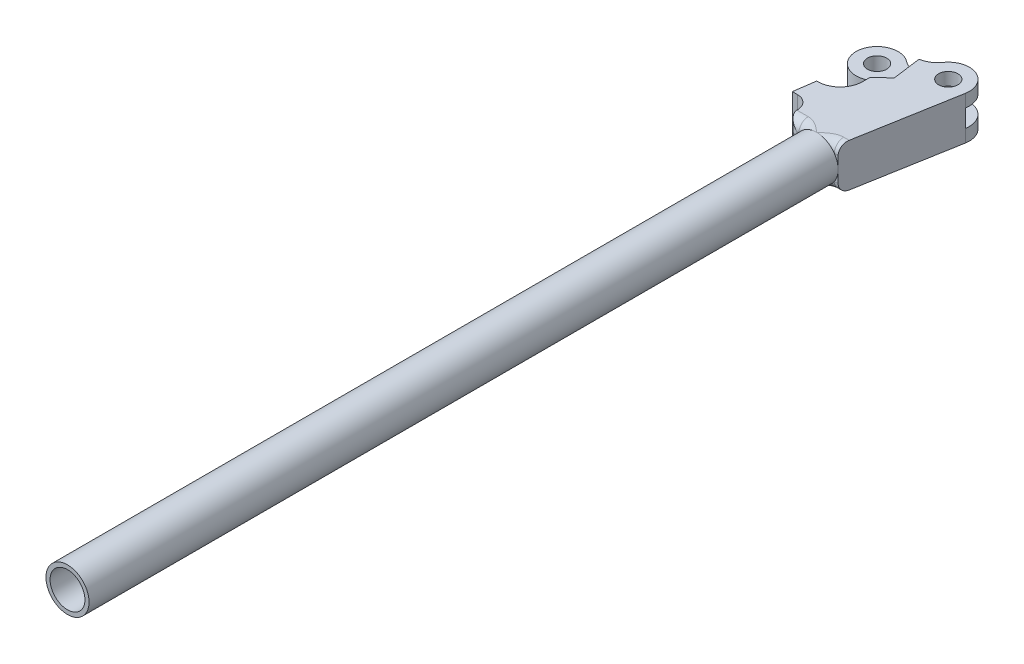
SolidWorks part; units mm, degrees
material "1.7243 (18CrMo4)"
ref_plane "Alzado" through (0, 0, 0) normal (0, 0, 1) x (1, 0, 0)
ref_plane "Planta" through (0, 0, 0) normal (0, 1, 0) x (1, 0, 0)
ref_plane "Vista lateral" through (0, 0, 0) normal (1, 0, 0) x (0, 0, -1)
sketch "Croquis1" plane through (0, 0, 0) normal (0, 0, 1) x (1, 0, 0)
  circle A0 centre (0, 0) radius 9.3
  circle A1 centre (0, 0) radius 11.5
  dimension "D1" = 18.6
  dimension "D2" = 23
extrude "Saliente-Extruir1" add sketch "Croquis1" along normal blind 400
sketch "Croquis2" plane through (0, 0, 0) normal (0, 0, -1) x (-1, 0, 0)
  line L1 (-27, -11.5) -> (27, -11.5)
  line L2 (-27, -11.5) -> (-27, 11.5)
  line L3 (-27, 11.5) -> (27, 11.5)
  line L4 (27, -11.5) -> (27, 11.5)
  line L5 (-27, -11.5) -> (27, 11.5) construction
  line L6 (-27, 11.5) -> (27, -11.5) construction
  point P0 (0, 0)
  dimension "D1" = 23
  dimension "D2" = 54
extrude "Saliente-Extruir2" add sketch "Croquis2" along normal blind 78.8
sketch "Croquis3" plane through (0, 11.5, 0) normal (0, 1, 0) x (1, 0, 0)
  line L0 (0, 0) -> (11.5, 0) construction
  line L1 (0, 0) -> (27, 0) construction
  line L5 (11.5, 0) -> (25.3946, 78.8)
  line L6 (-27, 78.8) -> (27, 78.8) construction
  line L7 (11.5, 0) -> (27, 0)
  line L8 (27, 0) -> (27, 78.8)
  line L9 (27, 78.8) -> (25.3946, 78.8)
  dimension "D1" = 11.5
  dimension "D2" = 80
extrude "Cortar-Extruir1" cut sketch "Croquis3" against normal blind 23
sketch "Croquis4" plane through (0, 11.5, 0) normal (0, 1, 0) x (1, 0, 0)
  line L0 (0.0968, 0) -> (10.6198, 59.6793)
  line L1 (10.6198, 59.6793) -> (-22.3802, 59.6793) construction
  line L2 (-22.3802, 59.6793) -> (-22.3802, 54.6793) construction
  line L3 (-25.3191, 18.04) -> (14.6809, 18.04) construction
  line L4 (-5.3191, 18.04) -> (-5.3191, 0) construction
  line L5 (-11.1502, 54.6793) -> (-11.1502, 35.74)
  line L6 (-23.1502, 23.74) -> (-25.3191, 23.74)
  line L7 (-15.5376, 0) -> (-5.3191, 0)
  line L8 (0, 0) -> (11.5, 0) construction
  line L9 (25.3946, 78.8) -> (11.5, 0) construction
  line L10 (-25.3191, 23.74) -> (-25.3191, 12.34)
  line L11 (-25.3191, 12.34) -> (-22.5376, 12.34)
  line L12 (-15.5376, 5.34) -> (-15.5376, 0)
  line L13 (-27, 0) -> (0, 0) construction
  circle A1 centre (10.6198, 59.6793) radius 5.15
  circle A2 centre (10.6198, 59.6793) radius 11.23
  circle A3 centre (-22.3802, 54.6793) radius 5.15
  circle A4 centre (-22.3802, 54.6793) radius 11.23
  arc A5 (-15.5376, 5.34) -> (-22.5376, 12.34) centre (-22.5376, 5.34) ccw
  arc A6 (-11.1502, 35.74) -> (-23.1502, 23.74) centre (-23.1502, 35.74) cw
  dimension "D2" = 11.23
  dimension "D3" = 10.3
  dimension "D4" = 22.46
  dimension "D7" = 22.46
  dimension "D8" = 10.3
  dimension "D11" = 7
  dimension "D13" = 12
  dimension "D1" = 60.6
  dimension "D5" = 33
  dimension "D6" = 5
  dimension "D9" = 40
  dimension "D10" = 18.04
  dimension "D12" = 11.4
extrude "Cortar-Extruir2" cut sketch "Croquis4" against normal blind 23 contours A1
sketch "Croquis5" plane through (0, 11.5, 0) normal (0, 1, 0) x (1, 0, 0)
  circle A0 centre (-22.3802, 54.6793) radius 11.23
extrude "Saliente-Extruir4" add sketch "Croquis5" against normal blind 23
extrude "Cortar-Extruir4" cut sketch "Croquis4<6>" against normal blind 23 contours A3
sketch "Croquis4<6>" plane through (0, 11.5, 0) normal (0, 1, 0) x (1, 0, 0) same geometry as "Croquis4"
sketch "Croquis6" plane through (0, 11.5, 0) normal (0, 1, 0) x (1, 0, 0)
  line L0 (-27, 78.8) -> (-27, 64.9151)
  line L1 (-27, 78.8) -> (25.3946, 78.8)
  line L3 (21.6792, 57.7293) -> (25.3946, 78.8)
  arc A0 (-15.4635, 63.5265) -> (1.3928, 66.0805) centre (-8.2415, 72.7643) ccw
  arc A2 (-15.4635, 63.5265) -> (-27, 64.9151) centre (-22.3802, 54.6793) ccw
  arc A4 (21.6792, 57.7293) -> (1.3928, 66.0805) centre (10.6198, 59.6793) ccw
extrude "Cortar-Extruir6" cut sketch "Croquis6" against normal blind 23
sketch "Croquis7" plane through (0, 11.5, 0) normal (0, 1, 0) x (1, 0, 0)
  line L0 (-11.1502, 54.6793) -> (-11.1502, 35.74)
  line L1 (-27, 44.4436) -> (-27, 0)
  line L2 (-27, 0) -> (-15.5376, 0)
  line L3 (-15.5376, 0) -> (-15.5376, 5.34)
  line L4 (-22.5376, 12.34) -> (-25.3191, 12.34)
  line L5 (-25.3191, 12.34) -> (-25.3191, 23.74)
  line L6 (-25.3191, 23.74) -> (-23.1502, 23.74)
  arc A0 (-27, 44.4436) -> (-11.1502, 54.6793) centre (-22.3802, 54.6793) ccw
  arc A1 (-23.1502, 23.74) -> (-11.1502, 35.74) centre (-23.1502, 35.74) ccw
  arc A2 (-15.5376, 5.34) -> (-22.5376, 12.34) centre (-22.5376, 5.34) ccw
extrude "Cortar-Extruir7" cut sketch "Croquis7" against normal blind 23
fillet "Redondeo2" radius 5 5 edges at (5.75, -11.5, 0) (-7.7688, -11.5, 0) (5.75, 11.5, 0) (-7.7688, 11.5, 0) (-15.5376, 0, 0)
fillet "Redondeo3" radius 5 1 edges at (-11.1502, 0, -54.6793) type face fillet first side face at (-11.1502, 0, -45.2097) second side face at (-22.8906, 0, -54.4305)
sketch "Croquis11" plane through (0, 11.5, 0) normal (0, 1, 0) x (1, 0, 0)
  circle A0 centre (10.6198, 59.6793) radius 11.23
extrude "Cortar-Extruir9" cut sketch "Croquis11" against normal blind 4.72 and the other way blind 4.72 from offset 11.5 contours A0 offset against normal yes
sketch "Croquis13" plane through (0, 11.5, 0) normal (0, 1, 0) x (1, 0, 0)
  circle A0 centre (-22.3802, 54.6793) radius 11.23
extrude "Cortar-Extruir11" cut sketch "Croquis13" against normal blind 6.78
sketch "Croquis14" plane through (0, -11.5, 0) normal (0, -1, 0) x (1, 0, 0)
  circle A0 centre (-22.3802, -54.6793) radius 11.23
extrude "Cortar-Extruir12" cut sketch "Croquis14" against normal blind 6.78
sketch "Croquis15" plane through (0, 11.5, 0) normal (0, 1, 0) x (1, 0, 0)
  line L0 (-11.1502, 39.6927) -> (-4.4014, 45.8886)
  line L1 (-4.4014, 45.8886) -> (-6.4849, 61.1709)
  arc A1 (-18.0694, 44.3097) -> (-15.4635, 63.5265) centre (-22.3802, 54.6793) ccw
  arc A2 (-15.4635, 63.5265) -> (-6.4849, 61.1709) centre (-8.2415, 72.7643) ccw
  arc A3 (-11.1502, 39.6927) -> (-18.0694, 44.3097) centre (-16.1502, 39.6927) ccw
extrude "Cortar-Extruir14" cut sketch "Croquis15" against normal blind 6.78
sketch "Croquis16" plane through (0, -11.5, 0) normal (0, -1, 0) x (1, 0, 0)
  line L0 (-11.1502, -39.6927) -> (-4.4014, -45.8886)
  line L1 (-4.4014, -45.8886) -> (-6.4849, -61.1709)
  arc A0 (-15.4635, -63.5265) -> (-18.0694, -44.3097) centre (-22.3802, -54.6793) ccw
  arc A1 (-6.4849, -61.1709) -> (-15.4635, -63.5265) centre (-8.2415, -72.7643) ccw
  arc A2 (-18.0694, -44.3097) -> (-11.1502, -39.6927) centre (-16.1502, -39.6927) ccw
extrude "Cortar-Extruir15" cut sketch "Croquis16" against normal blind 6.78
sketch "Croquis17" plane through (0, 11.5, 0) normal (0, 1, 0) x (1, 0, 0)
  line L0 (21.8498, 59.6793) -> (-6.2816, 59.6793)
  line L1 (-4.4014, 45.8886) -> (-6.4849, 61.1709) construction
  line L2 (-6.2816, 59.6793) -> (-8.2415, 72.7643)
  line L3 (-8.2415, 72.7643) -> (10.6198, 70.9093)
  arc A1 (21.8498, 59.6793) -> (10.6198, 70.9093) centre (10.6198, 59.6793) ccw
extrude "Cortar-Extruir16" cut sketch "Croquis17" against normal blind 4.72 and the other way blind 4.72 from offset 11.5 offset against normal yes
sketch "Croquis18" plane through (0, 11.5, 0) normal (0, 1, 0) x (1, 0, 0)
  line L0 (-25.3191, 23.74) -> (-25.3191, 12.34)
  line L1 (-25.3191, 12.34) -> (-23.5803, 12.34)
  line L2 (-23.5803, 12.34) -> (-25.3191, 23.74)
sketch "Croquis20" plane through (0, 11.5, 0) normal (0, 1, 0) x (1, 0, 0)
  line L0 (-25.3191, 12.34) -> (-25.3191, 23.74)
  line L1 (-25.3191, 23.74) -> (-24.2346, 23.74)
  line L2 (-25.3191, 23.74) -> (-23.1502, 23.74) construction
  line L3 (-24.2346, 23.74) -> (-25.3191, 12.34)
extrude "Cortar-Extruir19" cut sketch "Croquis20" against normal blind 23
sketch "Croquis21" plane through (0, 11.5, 0) normal (0, 1, 0) x (1, 0, 0)
  line L0 (-24.2346, 23.74) -> (-23.6924, 23.74)
  line L1 (-24.2346, 23.74) -> (-23.1502, 23.74) construction
  line L2 (-23.6924, 23.74) -> (-25.3191, 12.34)
  line L3 (-25.3191, 12.34) -> (-24.2346, 23.74)
extrude "Cortar-Extruir20" cut sketch "Croquis21" against normal blind 23
